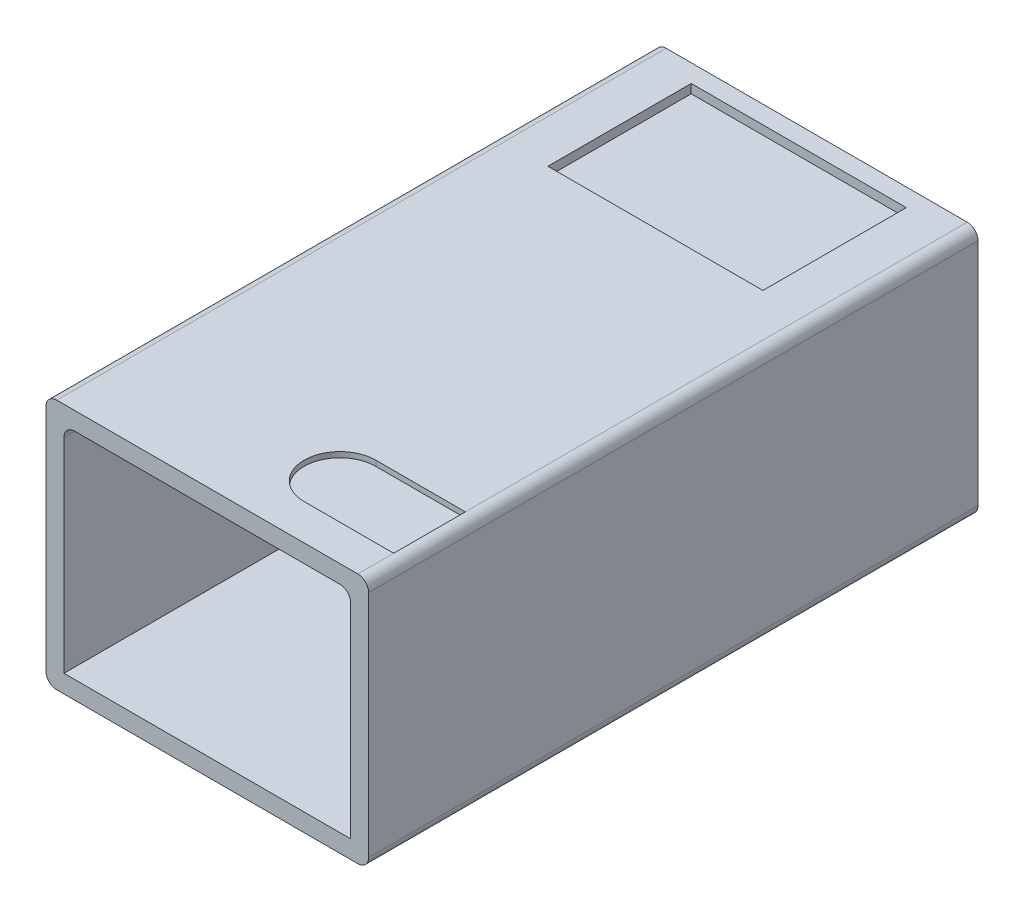
SolidWorks part; units mm, degrees
ref_plane "Front Plane" through (0, 0, 0) normal (0, 0, 1) x (1, 0, 0)
ref_plane "Top Plane" through (0, 0, 0) normal (0, 1, 0) x (1, 0, 0)
ref_plane "Right Plane" through (0, 0, 0) normal (1, 0, 0) x (0, 0, -1)
sketch "Sketch1" plane through (0, 0, 0) normal (0, 0, 1) x (1, 0, 0)
  line L1 (-37, 30) -> (37, 30)
  line L2 (-40, 27) -> (-40, -30)
  line L3 (-40, -30) -> (40, -30)
  line L4 (40, 27) -> (40, -30)
  line L5 (-40, 30) -> (40, -30) construction
  line L6 (-40, -30) -> (40, 30) construction
  line L7 (-42, 35) -> (42, 35)
  line L8 (-45, 32) -> (-45, -32)
  line L9 (-42, -35) -> (42, -35)
  line L10 (45, 32) -> (45, -32)
  line L11 (-45, 35) -> (45, -35) construction
  line L12 (-45, -35) -> (45, 35) construction
  arc A0 (42, -35) -> (45, -32) centre (42, -32) ccw
  arc A1 (-45, -32) -> (-42, -35) centre (-42, -32) ccw
  arc A2 (42, 35) -> (45, 32) centre (42, 32) cw
  arc A3 (-42, 35) -> (-45, 32) centre (-42, 32) ccw
  arc A4 (37, 30) -> (40, 27) centre (37, 27) cw
  arc A5 (-37, 30) -> (-40, 27) centre (-37, 27) ccw
  point P0 (0, 0)
  point P6 (0, 0)
  dimension "D5" = 3
  dimension "D1" = 80
  dimension "D2" = 60
  dimension "D3" = 90
  dimension "D4" = 70
extrude "Boss-Extrude1" add sketch "Sketch1" along normal blind 168
extrude "Boss-Extrude2" add sketch "Sketch1<2>" against normal blind 2 contours L10 A0 L9 A1 L8 A3 L7 A2
sketch "Sketch1<2>" plane through (0, 0, 0) normal (0, 0, 1) x (1, 0, 0) same geometry as "Sketch1"
sketch "Sketch2" plane through (0, 35, 0) normal (0, 1, 0) x (1, 0, 0)
  line L0 (0, 7.4708) -> (0, -174.5414) construction
  line L1 (-103.4971, -83) -> (89.9354, -83) construction
  line L2 (-42, 2) -> (42, 2) construction
  line L3 (42, -168) -> (42, 2) construction
  line L4 (-30, -3) -> (30, -3)
  line L5 (-30, -3) -> (-30, -43)
  line L6 (-30, -43) -> (30, -43)
  line L7 (30, -3) -> (30, -43)
  line L8 (-30, -3) -> (30, -43) construction
  line L9 (-30, -43) -> (30, -3) construction
  line L10 (42, -158) -> (17, -158)
  line L11 (42, -158) -> (42, -138)
  line L12 (42, -138) -> (17, -138)
  line L14 (42, -168) -> (-42, -168) construction
  arc A0 (17, -158) -> (17, -138) centre (17, -148) cw
  point P7 (0, -23)
  dimension "D1" = 85
  dimension "D2" = 60
  dimension "D3" = 40
  dimension "D4" = 5
  dimension "D5" = 25
  dimension "D6" = 20
  dimension "D7" = 10
extrude "Cut-Extrude1" cut sketch "Sketch2" against normal blind 2.5 contours L7 L4 L5 L6 region at (0, 35, 23)
extrude "Cut-Extrude2" cut sketch "Sketch2<3>" against normal blind 1.5 contours L10 A0 L12 L11
sketch "Sketch2<3>" plane through (0, 35, 0) normal (0, 1, 0) x (1, 0, 0) same geometry as "Sketch2"
